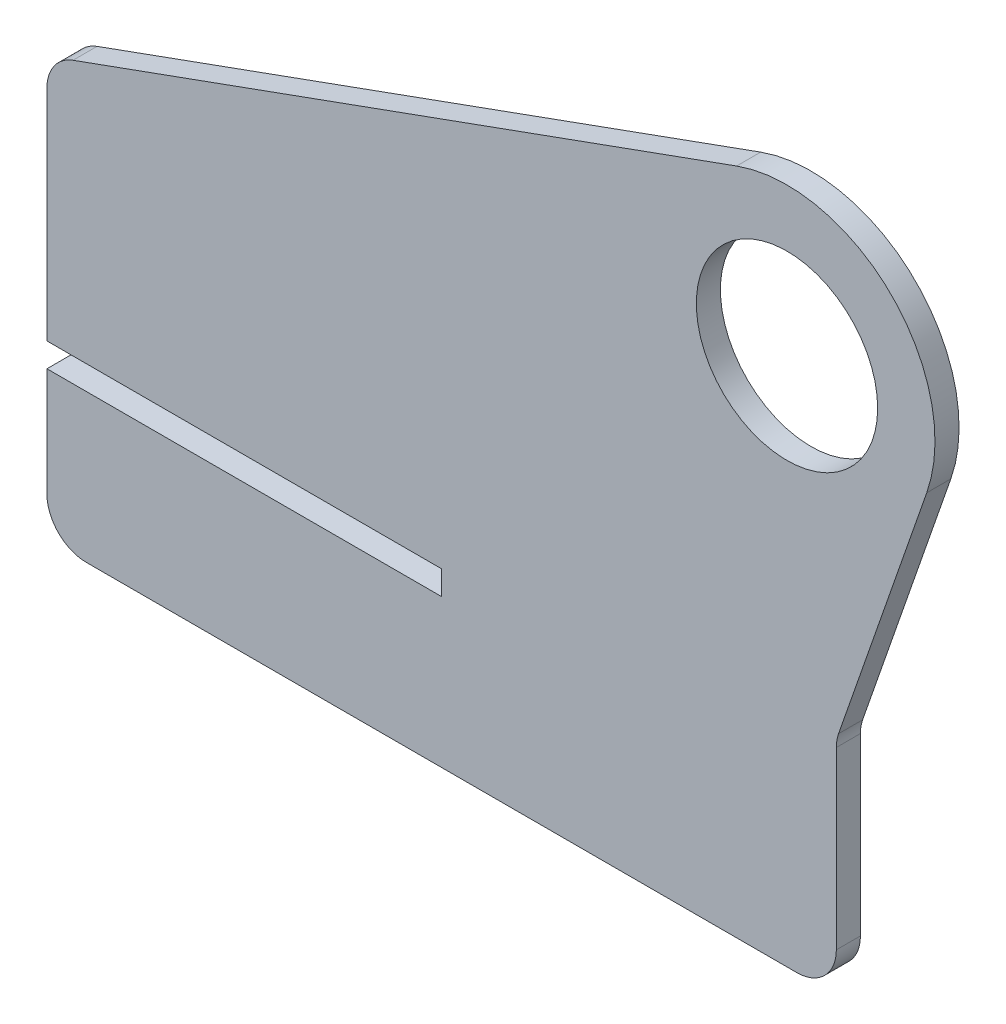
SolidWorks part; units mm, degrees
material "Corrugated Paper"
ref_plane "Front Plane" through (0, 0, 0) normal (0, 0, 1) x (1, 0, 0)
ref_plane "Top Plane" through (0, 0, 0) normal (0, 1, 0) x (1, 0, 0)
ref_plane "Right Plane" through (0, 0, 0) normal (1, 0, 0) x (0, 0, -1)
sketch "Sketch2" plane through (0, 0, 0) normal (0, 0, 1) x (1, 0, 0)
  line L0 (-50.8, 1.5494) -> (-50.8, 7.8994)
  line L1 (-50.8, -7.8994) -> (50.8, -7.8994)
  line L2 (-50.8, -7.8994) -> (-50.8, -1.5494)
  line L3 (-50.8, 7.8994) -> (50.8, 7.8994)
  line L4 (50.8, -7.8994) -> (50.8, 7.8994)
  line L5 (-50.8, -7.8994) -> (50.8, 7.8994) construction
  line L6 (-50.8, 7.8994) -> (50.8, -7.8994) construction
  line L7 (-50.8, 1.5494) -> (0, 1.5494)
  line L9 (-50.8, -1.5494) -> (0, -1.5494)
  line L10 (0, 1.5494) -> (0, -1.5494)
  point P0 (0, 0)
  dimension "D1" = 50.8
  dimension "D3" = 3.0988
  dimension "D2" = 6.35
extrude "Boss-Extrude1" add sketch "Sketch2" along normal blind 3.0988
sketch "Sketch3" plane through (0, 0, 0) normal (0, 0, 1) x (1, 0, 0)
  line L0 (-50.8, -7.8994) -> (-50.8, -20.5994)
  line L1 (-50.8, -20.5994) -> (101.6, -20.5994)
  line L2 (101.6, -20.5994) -> (101.6, 33.2994)
  line L3 (50.8, 7.8994) -> (-50.8, 7.8994) construction
  line L5 (-50.8, 33.2994) -> (-50.8, 7.8994)
  line L6 (-50.8, -7.8994) -> (50.8, -7.8994) construction
  line L7 (50.8, -7.8994) -> (50.8, 7.8994) construction
  line L8 (-50.8, -7.8994) -> (50.8, -7.8994)
  line L9 (50.8, -7.8994) -> (50.8, 7.8994)
  line L10 (50.8, 7.8994) -> (-50.8, 7.8994)
  line L12 (54.7822, 63.5237) -> (101.6, 33.2994)
  line L13 (37.9659, 65.4316) -> (-50.8, 33.2994)
  circle A0 centre (76.2, 0) radius 1.0795
  circle A1 centre (44.45, 47.519) radius 11.6713
  arc A2 (54.7822, 63.5237) -> (37.9659, 65.4316) centre (44.45, 47.519) ccw
  dimension "D1" = 2.159
  dimension "D7" = 38.1
  dimension "D8" = 23.3426
  dimension "D2" = 12.7
  dimension "D3" = 25.4
  dimension "D4" = 152.4
  dimension "D5" = 25.4
  dimension "D6" = 57.15
  dimension "D9" = 31.75
extrude "Boss-Extrude2" add sketch "Sketch3" along normal blind 3.0988 contours L10 L9 L8 L0 L1 L2 L5 A0 region at (31.2043, 17.2034, 0)
sketch "Sketch4" plane through (0, 0, 3.0988) normal (0, 0, 1) x (1, 0, 0)
  line L0 (62.4362, 41.2421) -> (50.8, 7.8994)
  line L2 (50.8, 7.8994) -> (50.8, -20.5994)
  line L11 (37.9659, 65.4316) -> (-50.8, 33.2994)
  line L12 (-50.8, 33.2994) -> (-50.8, 1.5494)
  line L13 (-50.8, 1.5494) -> (0, 1.5494)
  line L14 (0, 1.5494) -> (0, -1.5494)
  line L15 (0, -1.5494) -> (-50.8, -1.5494)
  line L16 (-50.8, -1.5494) -> (-50.8, -20.5994)
  line L17 (-50.8, -20.5994) -> (101.6, -20.5994)
  line L18 (101.6, -20.5994) -> (101.6, 33.2994)
  line L19 (101.6, 33.2994) -> (54.7822, 63.5237)
  line L20 (37.9659, 65.4316) -> (-50.8, 33.2994)
  line L21 (-50.8, 33.2994) -> (-50.8, 1.5494)
  line L22 (-50.8, 1.5494) -> (0, 1.5494)
  line L23 (0, 1.5494) -> (0, -1.5494)
  line L24 (0, -1.5494) -> (-50.8, -1.5494)
  line L25 (-50.8, -1.5494) -> (-50.8, -20.5994)
  line L26 (-50.8, -20.5994) -> (101.6, -20.5994)
  line L27 (101.6, -20.5994) -> (101.6, 33.2994)
  line L28 (101.6, 33.2994) -> (54.7822, 63.5237)
  circle A1 centre (44.45, 47.519) radius 19.05
  arc A2 (54.7822, 63.5237) -> (37.9659, 65.4316) centre (44.45, 47.519) ccw construction
  arc A4 (54.7822, 63.5237) -> (37.9659, 65.4316) centre (44.45, 47.519) ccw
  arc A5 (54.7822, 63.5237) -> (37.9659, 65.4316) centre (44.45, 47.519) ccw
  line M18 (-50.8, -20.5994) -> (101.6, -20.5994)
  line M19 (101.6, -20.5994) -> (101.6, 33.2994)
  line M20 (101.6, 33.2994) -> (54.7822, 63.5237)
  circle M22 centre (76.2, 0) radius 1.0795
  dimension "D1" = 0
extrude "Cut-Extrude1" cut sketch "Sketch4" against normal through all contours A1 M18 M19 M20 M22 region at (76.8337, 11.4389, 3.0988)
fillet "Fillet1" radius 5.08 4 edges at (-50.8, -20.5994, 1.5494) (-50.8, 33.2994, 1.5494) (50.8, 7.8994, 1.5494) (50.8, -20.5994, 1.5494)
equation "\"rodThick\"= 0.085in"
equation "\"thick\"= 0.122in"
equation "\"clear\"= 0.003in"
equation "\"D3@Sketch2\"=\"thick\""
equation "\"D1@Boss-Extrude1\"=\"thick\""
equation "\"D1@Sketch3\"=\"rodThick\""
equation "\"D1@Boss-Extrude2\"=\"thick\""
equation "\"D8@Sketch3\"=\"MotorDiameter@Motor-1.Part\""
